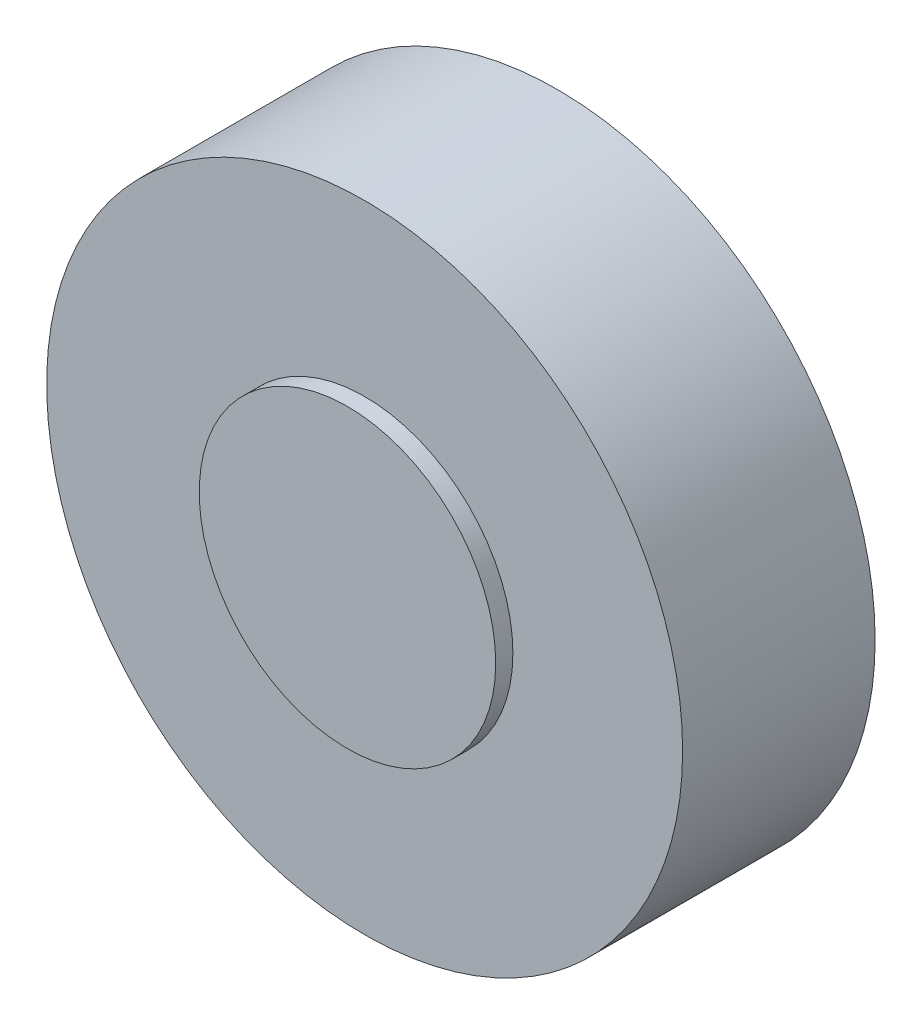
SolidWorks part; units mm, degrees
ref_plane "Front Plane" through (0, 0, 0) normal (0, 0, 1) x (1, 0, 0)
ref_plane "Top Plane" through (0, 0, 0) normal (0, 1, 0) x (1, 0, 0)
ref_plane "Right Plane" through (0, 0, 0) normal (1, 0, 0) x (0, 0, -1)
sketch "草图1" plane through (0, 0, 0) normal (0, 0, 1) x (1, 0, 0)
  circle A0 centre (0, 0) radius 74
  dimension "D1" = 148
extrude "凸台-拉伸1" add sketch "草图1" along normal blind 44.8
sketch "草图3" plane through (0, 0, 44.8) normal (0, 0, 1) x (1, 0, 0)
  circle A0 centre (0, 0) radius 34.5
  dimension "D1" = 69
extrude "凸台-拉伸2" add sketch "草图3" along normal blind 4
sketch "草图4" plane through (0, 0, 0) normal (0, 0, -1) x (1, 0, 0)
  line L5 (55.4546, -11.5723) -> (0, 0)
  line L6 (48.9576, -0.807) -> (55.4546, -11.5723)
  line L7 (56.6507, 10.3087) -> (48.9576, -0.807)
  line L8 (0, 0) -> (56.6507, 10.3087)
extrude "切除-拉伸3" cut sketch "草图4" against normal blind 4
ref_point "点1"
ref_axis "基准轴1" through (0, 0, 44.8) along (0, 0, -1)
